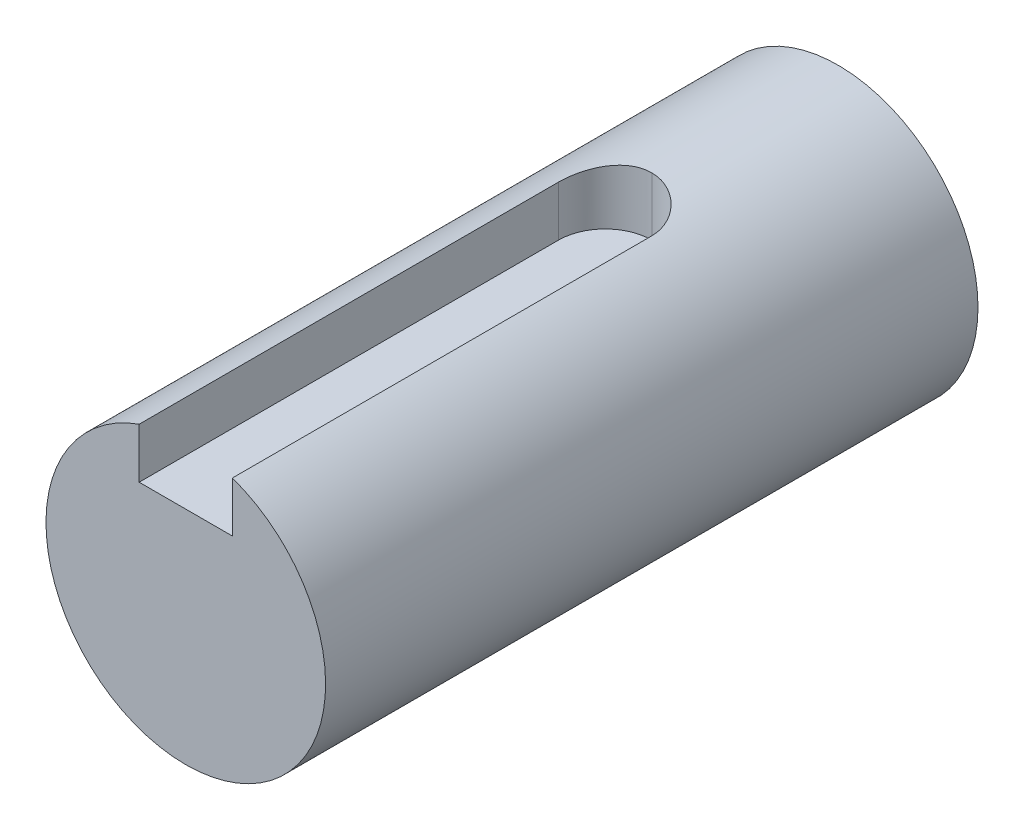
SolidWorks part; units mm, degrees
ref_plane "Front Plane" through (0, 0, 0) normal (0, 0, 1) x (1, 0, 0)
ref_plane "Top Plane" through (0, 0, 0) normal (0, 1, 0) x (1, 0, 0)
ref_plane "Right Plane" through (0, 0, 0) normal (1, 0, 0) x (0, 0, -1)
sketch "Sketch1" plane through (0, 0, 0) normal (0, 0, 1) x (1, 0, 0)
  circle A0 centre (0, 0) radius 6
  dimension "D1" = 12
extrude "Boss-Extrude1" add sketch "Sketch1" along normal blind 28
sketch "Sketch2" plane through (0, 0, 28) normal (0, 0, 1) x (1, 0, 0)
  line L0 (0, 6) -> (0, 3.5) construction
  line L2 (2, 3.5) -> (-2, 3.5)
  line L3 (2, 3.5) -> (2, 6)
  line L4 (2, 6) -> (-2, 6)
  line L5 (-2, 3.5) -> (-2, 6)
  circle A0 centre (0, 0) radius 6 construction
  point P10 (0, 3.5)
  dimension "D1" = 2.5
  dimension "D2" = 4
extrude "Cut-Extrude1" cut sketch "Sketch2" against normal blind 20
fillet "Fillet2" radius 2 1 edges at (-2, 4.5784, 8)
fillet "Fillet3" radius 2 1 edges at (2, 4.5784, 8)
